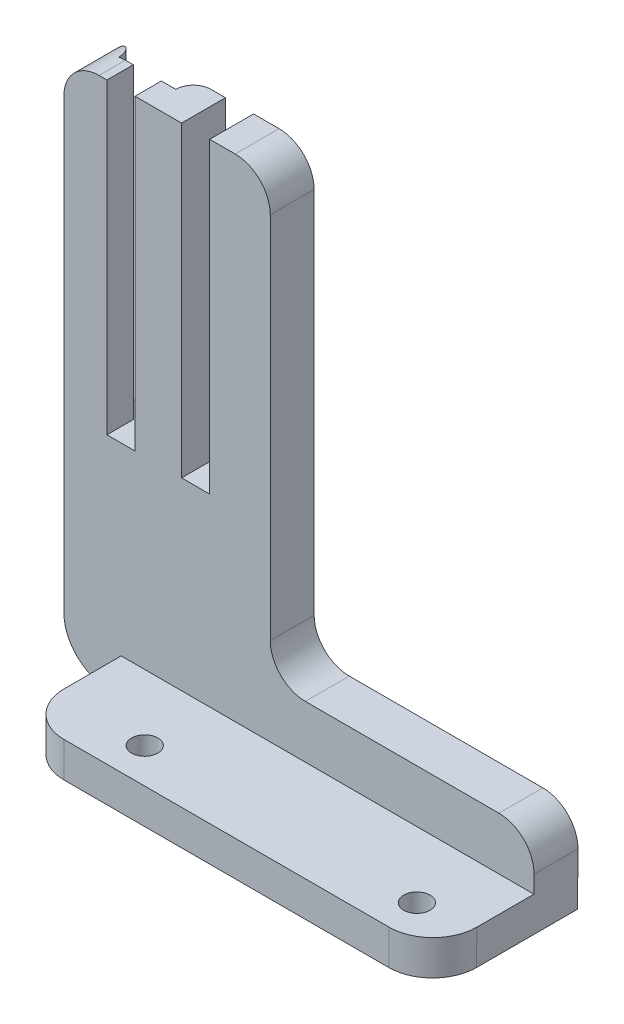
SolidWorks part; units mm, degrees
material "ABS generico"
ref_plane "Front Plane" through (0, 0, 0) normal (0, 0, 1) x (1, 0, 0)
ref_plane "Top Plane" through (0, 0, 0) normal (0, 1, 0) x (1, 0, 0)
ref_plane "Right Plane" through (0, 0, 0) normal (1, 0, 0) x (0, 0, -1)
sketch "Sketch1" plane through (0, 0, 0) normal (0, 0, 1) x (1, 0, 0)
  line L0 (24.5834, -25) -> (24.6606, -15)
  line L1 (24.5834, -25) -> (-28.9167, -25)
  line L2 (-5.4167, 0) -> (-5.4167, 35) construction
  line L3 (-5.4167, 35) -> (-12.3167, 35)
  line L5 (22.0833, -25) -> (-28.9167, 32.7358) construction
  line L6 (24.6606, -15) -> (-5.4167, -15)
  line L7 (-13.9167, 0) -> (-13.9167, 35) construction
  line L8 (-28.9167, -25) -> (-28.9167, 35)
  line L9 (24.5834, -15) -> (-30.9167, -15) construction
  line L10 (-12.3167, 0) -> (-12.3167, 35)
  line L11 (-15.5167, 0) -> (-15.5167, 35)
  line L12 (-5.4167, -15) -> (-5.4167, 35)
  line L13 (-24.0167, 35) -> (-28.9167, 35)
  line L14 (-15.5167, 35) -> (-20.8167, 35)
  line L15 (24.5834, -25) -> (-30.9167, -25) construction
  line L16 (-24.0167, 0) -> (-24.0167, 35)
  line L18 (-18, -10) -> (-18, 25) construction
  line L20 (-20.8167, 0) -> (-20.8167, 35)
  line L22 (-20.8167, 0) -> (-24.0167, 0)
  line L24 (-12.3167, 0) -> (-15.5167, 0)
  line L25 (-15.5167, -15) -> (-15.5167, 35) construction
  line L26 (-13.9167, -15) -> (-13.9167, 35) construction
  line L27 (-12.3167, -15) -> (-12.3167, 35) construction
  point P0 (0, 0)
  point P1 (-30.9167, 35)
  point P3 (26.5, 35)
  point P6 (-18, -25)
  point P10 (-16.4, -25)
  point P12 (-19.6, -25)
  point P18 (22.2762, 0)
  point P19 (-26.5, -10)
  dimension "D3" = 10
  dimension "D7" = 1.6
  dimension "D8" = 1.6
  dimension "D9" = 8.5
extrude "Extrude1" add sketch "Sketch1" along normal blind 5
sketch "Sketch3" plane through (0, 0, 5) normal (0, 0, 1) x (1, 0, 0)
  line L0 (22.0833, -10.5045) -> (22.0833, -32.7354) construction
  line L2 (-15.5167, 0) -> (-15.5167, -46) construction
  line L3 (-15.5167, -23) -> (22.0833, -23) construction
  line L4 (3.2833, -23) -> (3.2833, 0) construction
  line L5 (-15.5167, -25) -> (35.4785, -25) construction
  line L6 (-22.3949, -21) -> (24.6143, -21)
  line L8 (-22.3949, -25) -> (24.5834, -25)
  line L9 (-22.3949, -25) -> (-22.3949, -21)
  line L10 (-15.5167, -21) -> (22.0833, -25) construction
  line L11 (-15.5167, -25) -> (22.0833, -21) construction
  line L12 (24.6143, -21) -> (24.5834, -25)
  line L13 (24.5834, -25) -> (24.6606, -15) construction
  line L14 (-28.9167, -25) -> (24.5834, -25) construction
  dimension "D1" = 2
extrude "Extrude2" add sketch "Sketch3" along normal blind 11.5
sketch "Sketch4" plane through (0, 35, 0) normal (0, 1, 0) x (1, 0, 0)
  line L0 (-20.8167, 0) -> (-24.0167, 0) construction
  line L1 (-25.6667, -2) -> (-19.1667, -2)
  line L2 (-25.6667, -2) -> (-25.6667, 2)
  line L3 (-25.6667, 2) -> (-19.1667, 2)
  line L4 (-19.1667, -2) -> (-19.1667, 2)
  line L5 (-25.6667, -2) -> (-19.1667, 2) construction
  line L6 (-25.6667, 2) -> (-19.1667, -2) construction
  point P0 (-22.4167, 0)
  dimension "D1" = 6.5
  dimension "D2" = 4
sketch "Sketch5" plane through (0, -21, 0) normal (0, 1, 0) x (1, 0, 0)
  line L0 (17.6784, -12.4986) -> (-11.1079, -12.5014) construction
  line L1 (3.2852, -12.5) -> (3.2852, -16.5) construction
  line L2 (-15.5167, -16.5) -> (22.0833, -16.5) construction
  circle A0 centre (-12.2148, -12.5015) radius 1.5
  circle A1 centre (18.7852, -12.5015) radius 1.5
  dimension "D1" = 3
  dimension "D2" = 15.5
  dimension "D3" = 4
extrude "Extrude3" cut sketch "Sketch5" against normal up to surface (4 mm away) up to face at (-9.4529, -25, 8.125)
fillet "Fillet2" radius 5 2 edges at (-22.3949, -23, 16.5) (24.5988, -23, 16.5)
fillet "Fillet3" radius 4 4 edges at (24.6606, -15, 2.5) (-5.4167, -15, 2.5) (-5.4167, 35, 2.5) (-28.9167, 35, 2.5)
fillet "Fillet4" radius 5 1 edges at (-28.9167, -25, 2.5)
extrude "Extrude4" cut sketch "Sketch4" against normal up to surface (35 mm away) up to face at (-22.4167, 0, 2.5)
fillet "Fillet1" radius 2 2 edges at (-19.1667, 17.5, 0) (-25.6667, 17.4645, 0)
